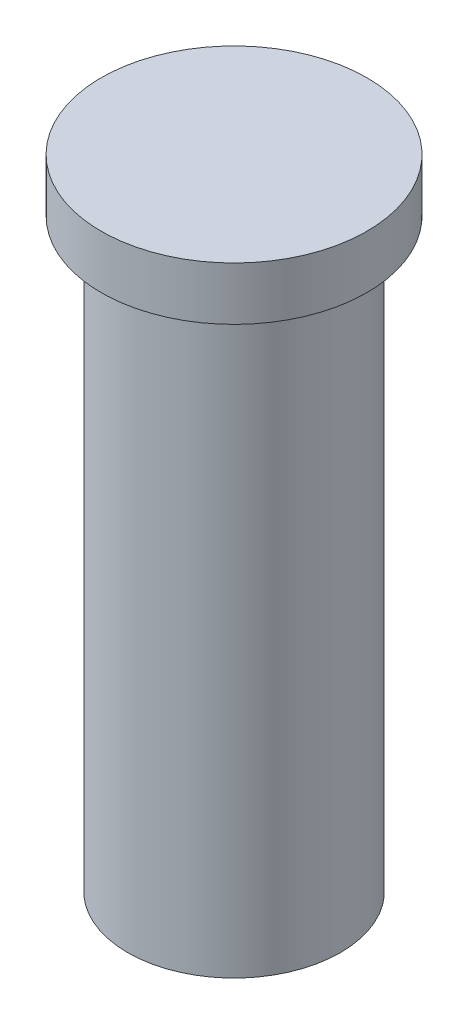
SolidWorks part; units mm, degrees
material "1060 Alloy"
ref_plane "Front Plane" through (0, 0, 0) normal (0, 0, 1) x (1, 0, 0)
ref_plane "Top Plane" through (0, 0, 0) normal (0, 1, 0) x (1, 0, 0)
ref_plane "Right Plane" through (0, 0, 0) normal (1, 0, 0) x (0, 0, -1)
sketch "Sketch1" plane through (0, 0, 0) normal (0, 0, 1) x (1, 0, 0)
  line L0 (0, 0) -> (0, 12) construction
  line L1 (0, 12) -> (2.5, 12)
  line L2 (2.5, 12) -> (2.5, 11)
  line L3 (2.5, 11) -> (2, 11)
  line L4 (2, 11) -> (2, 0)
  line L5 (2, 0) -> (0, 0)
  line L6 (0, 0) -> (0, 12)
  dimension "D1" = 4
  dimension "D2" = 5
  dimension "D3" = 12
  dimension "D4" = 11
revolve "Revolve1" add sketch "Sketch1" angle 360 about L0
